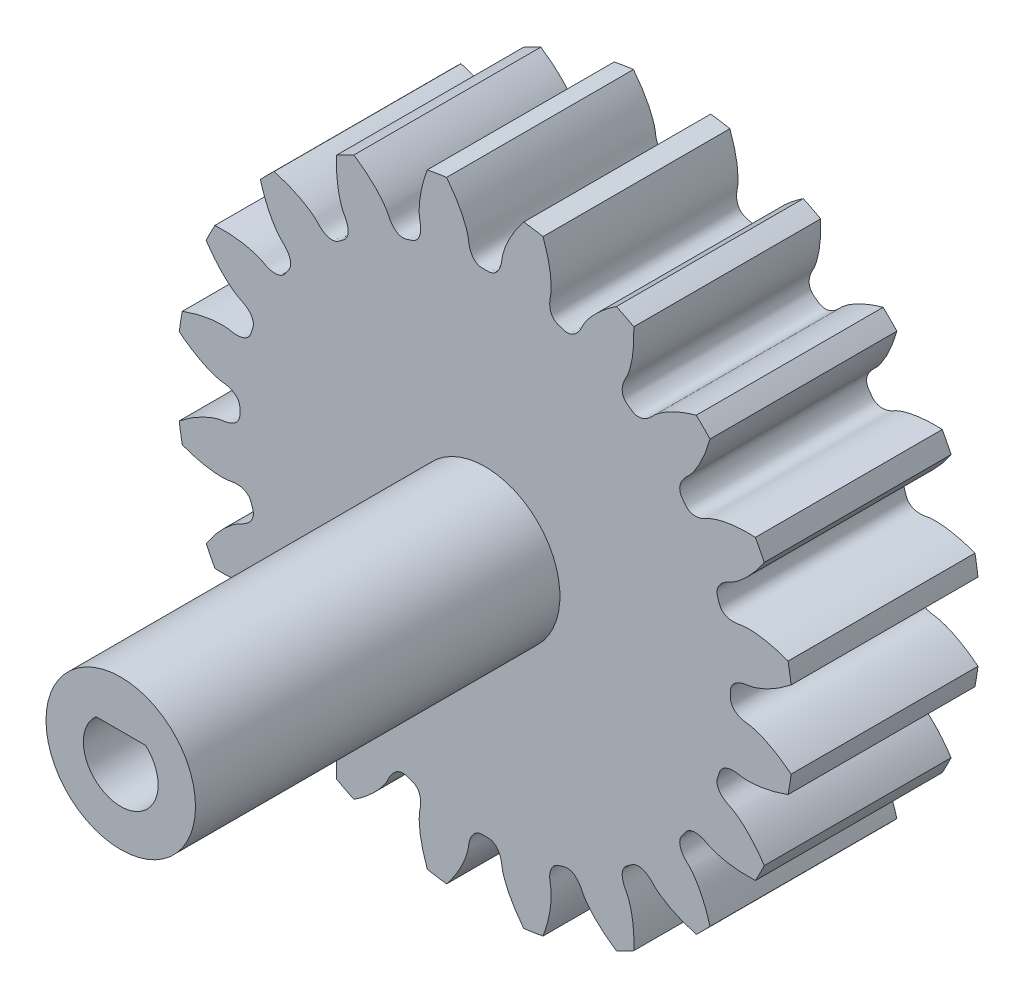
SolidWorks part; units mm, degrees
ref_plane "Front Plane" through (0, 0, 0) normal (0, 0, 1) x (1, 0, 0)
ref_plane "Top Plane" through (0, 0, 0) normal (0, 1, 0) x (1, 0, 0)
ref_plane "Right Plane" through (0, 0, 0) normal (1, 0, 0) x (0, 0, -1)
ref_axis "Axis1" through (0, 0, 55) along (0, 0, -1)
sketch "SketchRevolveSpurAssembly01Pinion" plane through (0, 0, 0) normal (1, 0, 0) x (0, 0, -1)
  line L0 (0, 0) -> (1, 0) construction
  line L1 (-5, 0) -> (-5, 16.5)
  line L2 (-5, 16.5) -> (5, 16.5)
  line L3 (5, 16.5) -> (5, 0)
  line L4 (5, 0) -> (-5, 0)
  dimension "Side1" = 5
  dimension "OutsideRadius" = 16.5
  dimension "Side2" = 5
revolve "SpurAssembly01Pinion" add sketch "SketchRevolveSpurAssembly01Pinion" angle 360 about L0
sketch "SketchToothSpurAssembly01Pinion" plane through (0, 0, 0) normal (0, 0, 1) x (1, 0, 0)
  arc A0 (16.4388, 2.1204) -> (16.4388, -2.1204) centre (0, 0) cw
  spline S0 degree 3 poles (16.4388, -2.1204) (16.3062, -2.0126) (16.1079, -1.8609) (15.8417, -1.6767) (15.6549, -1.5557) (15.4759, -1.4476) (15.3054, -1.3516) (15.1441, -1.2672) (14.9923, -1.1937) (14.8506, -1.1305) (14.7196, -1.0767) (14.5996, -1.0318) (14.491, -0.9949) (14.3942, -0.9653) (14.3096, -0.9423) (14.2375, -0.925) (14.178, -0.9126) (14.0492, -0.8903) (13.9123, -0.8782) (13.7697, -0.8427) (13.6956, -0.8206) (13.6244, -0.795) (13.5557, -0.7654) (13.4893, -0.7311) (13.4248, -0.6913) (13.3623, -0.6446) (13.3021, -0.5892) (13.2452, -0.523) (13.1943, -0.4439) (13.1533, -0.3509) (13.1303, -0.2534) (13.1208, -0.135) (13.1277, 0) (13.1208, 0.135) (13.1303, 0.2534) (13.1533, 0.3509) (13.1943, 0.4439) (13.2452, 0.523) (13.3021, 0.5892) (13.3623, 0.6446) (13.4248, 0.6913) (13.4893, 0.7311) (13.5557, 0.7654) (13.6244, 0.795) (13.6956, 0.8206) (13.7697, 0.8427) (13.9123, 0.8782) (14.0492, 0.8903) (14.178, 0.9126) (14.2375, 0.925) (14.3096, 0.9423) (14.3942, 0.9653) (14.491, 0.9949) (14.5996, 1.0318) (14.7196, 1.0767) (14.8506, 1.1305) (14.9923, 1.1937) (15.1441, 1.2672) (15.3054, 1.3516) (15.4759, 1.4476) (15.6549, 1.5557) (15.8417, 1.6767) (16.1079, 1.8609) (16.3062, 2.0126) (16.4388, 2.1204) knots 0 0 0 0 0.061423 0.08971 0.11638 0.141434 0.164872 0.186693 0.206898 0.225486 0.242459 0.257814 0.271554 0.283677 0.294183 0.303073 0.310347 0.316004 0.350077 0.359568 0.368803 0.377844 0.386769 0.395676 0.404689 0.413963 0.423683 0.434051 0.445256 0.457401 0.47042 0.481067 0.5 0.518933 0.52958 0.542599 0.554744 0.565949 0.576317 0.586037 0.595311 0.604324 0.613231 0.622156 0.631197 0.640432 0.649923 0.683996 0.689653 0.696927 0.705817 0.716323 0.728446 0.742186 0.757541 0.774514 0.793102 0.813307 0.835128 0.858566 0.88362 0.91029 0.938577 1 1 1 1
extrude "ToothExtrudeCutSpurAssembly01Pinion" cut sketch "SketchToothSpurAssembly01Pinion" against normal blind 5 and the other way blind 5
pattern_circular "PatternSpurAssembly01Pinion" count 20 every 18 about axis through (0, 0, 55) along (0, 0, -1) of "ToothExtrudeCutSpurAssembly01Pinion"
sketch "AuxiliarySketchSpurAssembly01Pinion" plane through (0, 0, 0) normal (0, 0, 1) x (1, 0, 0)
  circle A0 centre (0, 0) radius 15 construction
  circle A1 centre (0, 0) radius 14.0954 construction
  circle A2 centre (0, 0) radius 14.1048 construction
  circle A3 centre (0, 0) radius 16.5 construction
  circle A4 centre (0, 0) radius 13.125 construction
  dimension "PitchDiameter" = 30
  dimension "BaseDiameter" = 28.1908
  dimension "FormDiameter" = 28.2095
  dimension "MajorDiameter" = 33
  dimension "MinorDiameter" = 26.25
sketch "Sketch1" plane through (0, 0, 5) normal (0, 0, 1) x (1, 0, 0)
  circle A0 centre (0, 0) radius 4
extrude "Boss-Extrude1" add sketch "Sketch1" along normal blind 19.5
sketch "Sketch7" plane through (0, 0, 24.5) normal (0, 0, 1) x (1, 0, 0)
  line L0 (0, 0) -> (0, 1.5) construction
  line L1 (1.3229, 1.5) -> (-1.3229, 1.5)
  circle A0 centre (0, 0) radius 2 construction
  arc A1 (1.3229, 1.5) -> (-1.3229, 1.5) centre (0, 0) cw
  point P10 (0, 1.5)
extrude "Cut-Extrude5" cut sketch "Sketch7" against normal blind 8 contours L1 A1
sketch "Sketch8" plane through (0, 0, -5) normal (0, 0, -1) x (-1, 0, 0)
  circle A0 centre (0, 0) radius 4
extrude "Boss-Extrude5" add sketch "Sketch8" along normal blind 5
